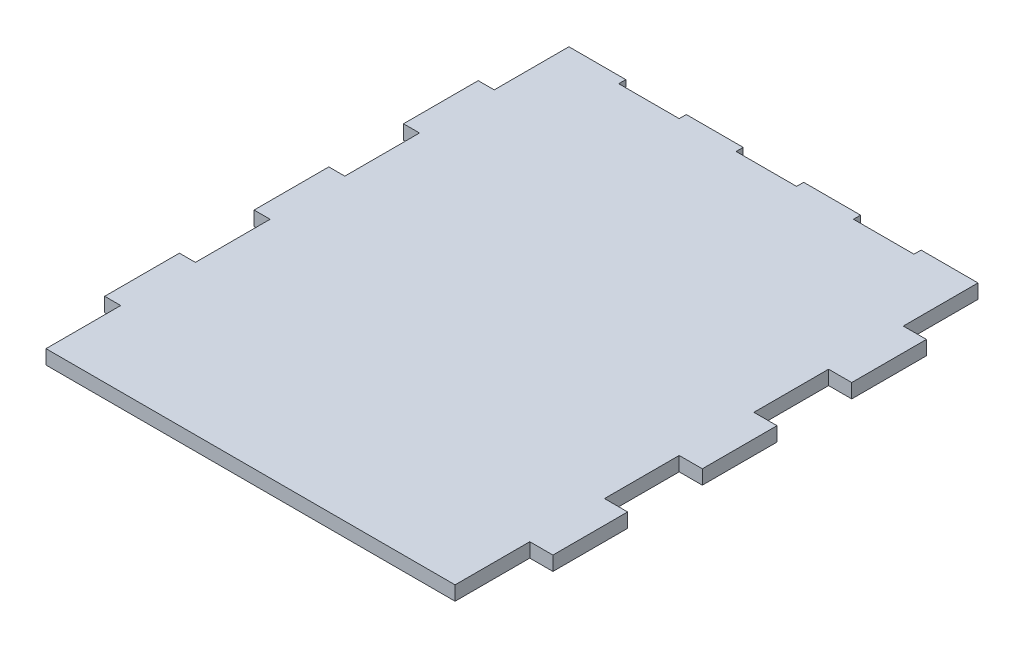
SolidWorks part; units mm, degrees
ref_plane "前视基准面" through (0, 0, 0) normal (0, 0, 1) x (1, 0, 0)
ref_plane "上视基准面" through (0, 0, 0) normal (0, 1, 0) x (1, 0, 0)
ref_plane "右视基准面" through (0, 0, 0) normal (1, 0, 0) x (0, 0, -1)
other "Configuration Table"
sketch "草图4" plane through (0, 0, 0) normal (0, 1, 0) x (1, 0, 0)
  line L6 (-57.5, -72.5) -> (57.5, -72.5)
  line L11 (-57.5, -72.5) -> (-57.5, 72.5)
  line L12 (-57.5, 72.5) -> (57.5, 72.5)
  line L13 (57.5, -72.5) -> (57.5, 72.5)
  line L14 (-57.5, -72.5) -> (57.5, 72.5) construction
  line L15 (-57.5, 72.5) -> (57.5, -72.5) construction
  point P0 (0, 0)
  dimension "D1" = 115
  dimension "D2" = 145
extrude "凸台-拉伸1" add sketch "草图4" along normal blind 4
sketch "草图5" plane through (0, 0, -72.5) normal (0, 0, -1) x (-1, 0, 0)
  line L0 (-57.5, 4) -> (57.5, 4) construction
  line L1 (57.5, 0) -> (41.5, 0)
  line L2 (57.5, 0) -> (57.5, 4)
  line L3 (57.5, 4) -> (41.5, 4)
  line L4 (41.5, 0) -> (41.5, 4)
  line L5 (-57.5, 0) -> (57.5, 0) construction
  line L6 (24.5, 0) -> (8.5, 0)
  line L7 (24.5, 0) -> (24.5, 4)
  line L8 (24.5, 4) -> (8.5, 4)
  line L9 (8.5, 0) -> (8.5, 4)
  line L10 (41.5, 0) -> (24.5, 0)
  line L11 (-8.5, 0) -> (-24.5, 0)
  line L12 (-8.5, 0) -> (-8.5, 4)
  line L13 (-8.5, 4) -> (-24.5, 4)
  line L14 (-24.5, 0) -> (-24.5, 4)
  line L15 (-41.5, 0) -> (-57.5, 0)
  line L16 (-41.5, 0) -> (-41.5, 4)
  line L17 (-41.5, 4) -> (-57.5, 4)
  line L18 (-57.5, 0) -> (-57.5, 4)
  line L19 (8.5, 0) -> (-8.5, 0)
  line L20 (-24.5, 0) -> (-41.5, 0)
  line M17 (-57.5, 0) -> (57.5, 0)
  line M18 (57.5, 0) -> (57.5, 4)
  line M19 (57.5, 4) -> (-57.5, 4)
  line M20 (-57.5, 4) -> (-57.5, 0)
  dimension "D1" = 17
extrude "凸台-拉伸2" add sketch "草图5" along normal blind 2 contours L16 M17 M19 M20 | L14 L12 M17 M19 | L9 L7 M17 M19 | L4 M17 M18 M19 region at (-49.5, 2, -72.5) region at (-16.5, 2, -72.5) region at (16.5, 2, -72.5) region at (49.5, 2, -72.5)
sketch "草图6" plane through (-57.5, 0, 0) normal (-1, 0, 0) x (0, 0, 1)
  line L0 (-74.5, 4) -> (72.5, 4) construction
  line L1 (-53.5, 4) -> (-32.5, 4)
  line L2 (-53.5, 4) -> (-53.5, 0)
  line L3 (-53.5, 0) -> (-32.5, 0)
  line L4 (-32.5, 4) -> (-32.5, 0)
  line L5 (-74.5, 0) -> (72.5, 0) construction
  line L6 (-74.5, 2) -> (-53.5, 2) construction
  line L7 (-11.5, 4) -> (9.5, 4)
  line L8 (-11.5, 4) -> (-11.5, 0)
  line L9 (-11.5, 0) -> (9.5, 0)
  line L10 (9.5, 4) -> (9.5, 0)
  line L11 (30.5, 4) -> (51.5, 4)
  line L12 (30.5, 4) -> (30.5, 0)
  line L13 (30.5, 0) -> (51.5, 0)
  line L14 (51.5, 4) -> (51.5, 0)
  line L15 (-74.5, 0) -> (-74.5, 4) construction
  line L16 (-53.5, 2) -> (-32.5, 2) construction
  line L17 (-32.5, 2) -> (-11.5, 2) construction
  line L18 (-11.5, 2) -> (9.5, 2) construction
  line L19 (9.5, 2) -> (30.5, 2) construction
  line L20 (30.5, 2) -> (51.5, 2) construction
  line L21 (51.5, 2) -> (72.5, 2) construction
  line L22 (72.5, 4) -> (72.5, 0) construction
extrude "凸台-拉伸3" add sketch "草图6" along normal blind 4.5
extrude "凸台-拉伸4" add sketch "草图6<2>" against normal blind 6.5 from surface starting at face at (57.5, 2, -1)
sketch "草图6<2>" plane through (-57.5, 0, 0) normal (-1, 0, 0) x (0, 0, 1) same geometry as "草图6"
sketch "草图7" plane through (0, 0, 72.5) normal (0, 0, 1) x (1, 0, 0)
  line L0 (-41.8, 0) -> (-44, 2.2)
  line L1 (-57.5, 0) -> (57.5, 0) construction
  line L2 (-44, 2.2) -> (-41.8, 2.2)
  line L3 (-41.8, 2.2) -> (-21.2, 2.2)
  line L4 (-21.2, 2.2) -> (-19, 2.2)
  line L5 (-19, 2.2) -> (-21.2, 0)
  line L6 (-21.2, 0) -> (-41.8, 0)
  line L7 (-41.8, 2.2) -> (-41.8, 0)
  line L8 (-21.2, 2.2) -> (-21.2, 0)
  line L9 (-31.5, 0) -> (-31.5, 2.2) construction
  line L10 (21.2, 0) -> (19, 2.2)
  line L11 (19, 2.2) -> (21.2, 2.2)
  line L12 (21.2, 2.2) -> (41.8, 2.2)
  line L13 (41.8, 2.2) -> (44, 2.2)
  line L14 (44, 2.2) -> (41.8, 0)
  line L15 (41.8, 0) -> (21.2, 0)
  line L16 (21.2, 2.2) -> (21.2, 0)
  line L17 (41.8, 2.2) -> (41.8, 0)
  line L18 (31.5, 0) -> (31.5, 2.2) construction
  line L19 (64, 0) -> (64, 4) construction
  line L20 (-62, 0) -> (-62, 4) construction
  line M10 (-57.5, 0) -> (57.5, 0)
  dimension "D1" = 20.6
  dimension "D2" = 2.2
  dimension "D3" = 20.6
  dimension "D4" = 2.2
  dimension "D5" = 32.5
  dimension "D6" = 30.5
extrude "切除-拉伸1" cut sketch "草图7" against normal through all from offset 1.8 contours L17 L12 L16 M10 | L8 L3 L7 M10 | L4 L8 L5 | L7 L2 L0 | L13 L17 L14 | L16 L11 L10 region at (20.4667, 1.4667, 72.5) region at (31.5, 1.1, 72.5) region at (-31.5, 1.1, 72.5) region at (-42.5333, 1.4667, 72.5) region at (-20.4667, 1.4667, 72.5) region at (42.5333, 1.4667, 72.5) offset against normal yes
sketch "草图8" plane through (0, 2.2, 0) normal (0, -1, 0) x (1, 0, 0)
  line L0 (-49.65, -74.5) -> (-41.8, -54.5)
  line L7 (-41.8, -74.5) -> (-57.5, -74.5) construction
  line L12 (-41.8, -74.5) -> (-41.8, 70.7) construction
  line L13 (-41.8, -54.5) -> (41.8, -54.5)
  line L14 (41.8, -74.5) -> (41.8, 70.7) construction
  line L15 (41.8, -54.5) -> (49.65, -74.5)
  line L16 (57.5, -74.5) -> (41.8, -74.5) construction
  line L17 (21.2, -74.5) -> (8.5, -74.5) construction
  line L18 (-49.65, -74.5) -> (49.65, -74.5)
  dimension "D1" = 20
extrude "切除-拉伸2" cut sketch "草图8" along normal through all
